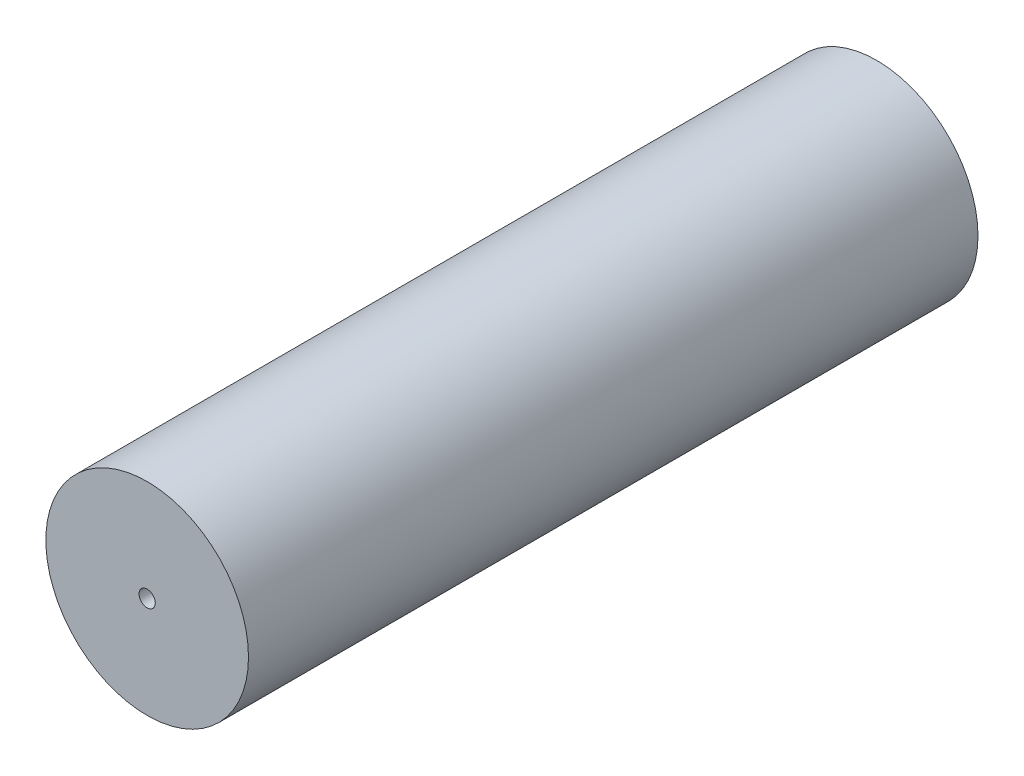
SolidWorks part; units mm, degrees
ref_plane "Front Plane" through (0, 0, 0) normal (0, 0, 1) x (1, 0, 0)
ref_plane "Top Plane" through (0, 0, 0) normal (0, 1, 0) x (1, 0, 0)
ref_plane "Right Plane" through (0, 0, 0) normal (1, 0, 0) x (0, 0, -1)
sketch "Sketch1" plane through (0, 0, 0) normal (0, 0, 1) x (1, 0, 0)
  circle A0 centre (0, 0) radius 125
  dimension "D1" = 250
extrude "Boss-Extrude1" add sketch "Sketch1" along normal blind 900
sketch "Sketch2" plane through (0, 0, 900) normal (0, 0, 1) x (1, 0, 0)
  circle A0 centre (0, 0) radius 10
  dimension "D1" = 20
extrude "Cut-Extrude1" cut sketch "Sketch2" against normal blind 200
sketch "Sketch3" plane through (0, 0, 0) normal (0, 0, -1) x (-1, 0, 0)
  circle A0 centre (0, 0) radius 10 construction
  circle A1 centre (0, 0) radius 10
extrude "Cut-Extrude2" cut sketch "Sketch3" against normal blind 200
